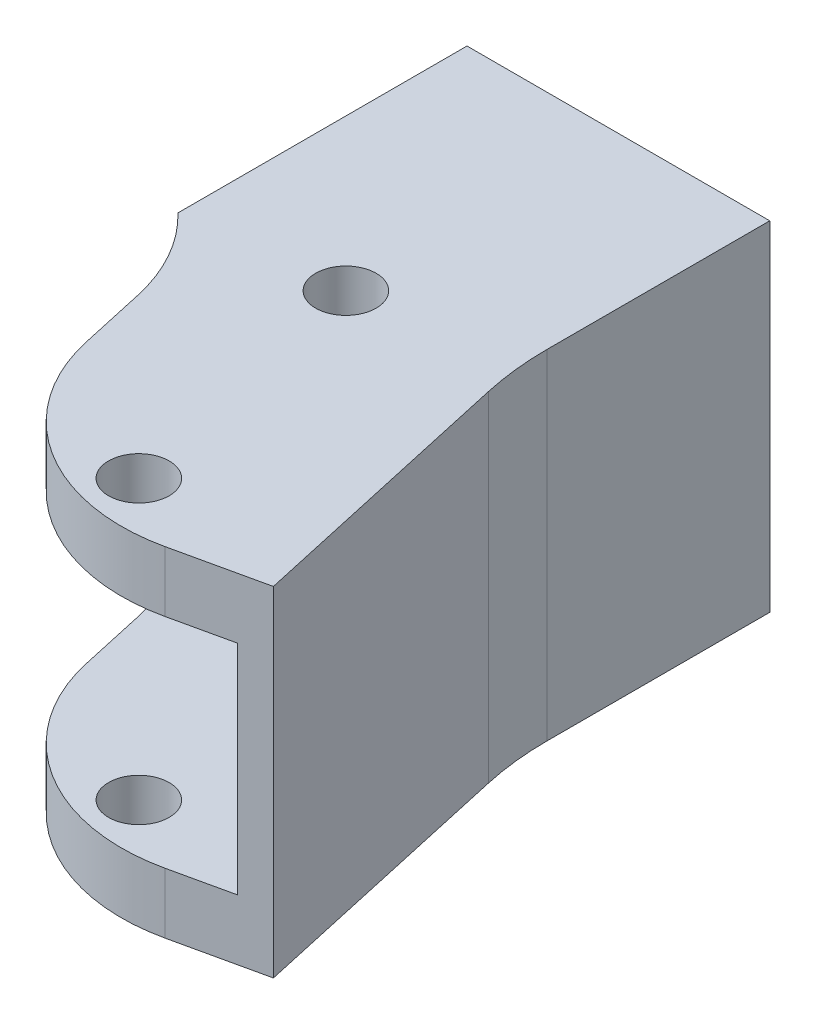
SolidWorks part; units mm, degrees
material "ABS"
ref_plane "正面" through (0, 0, 0) normal (0, 0, 1) x (1, 0, 0)
ref_plane "平面" through (0, 0, 0) normal (0, 1, 0) x (1, 0, 0)
ref_plane "右側面" through (0, 0, 0) normal (1, 0, 0) x (0, 0, -1)
sketch "ｽｹｯﾁ1" plane through (0, 0, 0) normal (0, 0, 1) x (1, 0, 0)
  line L1 (-20, 18) -> (20, 18)
  line L2 (-20, 18) -> (-20, -18)
  line L3 (-20, -18) -> (20, -18)
  line L4 (20, 18) -> (20, -18)
  line L5 (-20, 18) -> (20, -18) construction
  line L6 (-20, -18) -> (20, 18) construction
  circle A0 centre (0, 0) radius 8.5 construction
  circle A1 centre (0, 8.5) radius 1.6
  circle A2 centre (8.5, 0) radius 1.6
  circle A3 centre (0, -8.5) radius 1.6
  circle A4 centre (-8.5, 0) radius 1.6
  circle A5 centre (0, 0) radius 3.25
  point P0 (0, 0)
  point P19 (0, 0)
  dimension "D2" = 17
  dimension "D3" = 3.2
  dimension "D6" = 6.5
  dimension "D1" = 36
  dimension "D5" = 40
  dimension "D4" = 4
extrude "ﾎﾞｽ - 押し出し1" add sketch "ｽｹｯﾁ1" along normal blind 5
sketch "ｽｹｯﾁ2" plane through (0, 0, 5) normal (0, 0, 1) x (1, 0, 0)
  circle A0 centre (0, 0) radius 13
  dimension "D1" = 26
extrude "ｶｯﾄ - 押し出し1" cut sketch "ｽｹｯﾁ2" against normal blind 2.5
sketch "ｽｹｯﾁ7" plane through (0, -18, 0) normal (0, -1, 0) x (1, 0, 0)
  line L0 (-20, 0) -> (-20, 47.1904)
  line L1 (-20, 5) -> (-20, 0) construction
  line L2 (-20, 47.1904) -> (-7.6217, 103.0251)
  line L3 (-7.6217, 103.0251) -> (31.4301, 94.3675)
  line L4 (31.4301, 94.3675) -> (20, 42.8096)
  line L5 (20, 42.8096) -> (20, 0)
  line L6 (-20, 0) -> (20, 0) construction
  line L7 (20, 0) -> (-20, 0)
  line L8 (0, 0) -> (0, 42.348) construction
  line L9 (11.9042, 98.6963) -> (-8.4859, 6.7224) construction
  line L10 (20, 5) -> (20, 0) construction
  circle A0 centre (0, 45) radius 5
  circle A1 centre (9.7398, 88.9333) radius 5
  point P16 (-34.8258, 3.4356)
  point P19 (0, 0)
  point P20 (-30.3927, 17.0331)
  point P23 (0, 0)
  dimension "D1" = 10
  dimension "D4" = 10
  dimension "D2" = 40
  dimension "D3" = 45
  dimension "D5" = 12.5
  dimension "D6" = 45
extrude "ﾎﾞｽ - 押し出し2" add sketch "ｽｹｯﾁ7" along normal blind 10
sketch "ｽｹｯﾁ10" plane through (0, -18, 0) normal (0, 1, 0) x (1, 0, 0)
  circle A0 centre (0, -45) radius 5
  circle A1 centre (0, -45) radius 5 construction
extrude "ﾎﾞｽ - 押し出し4" add sketch "ｽｹｯﾁ10" against normal blind 2
mirror "ﾐﾗｰ3" about plane through (0, 0, 0) normal (0, 1, 0) of "ﾎﾞｽ - 押し出し4", "ﾎﾞｽ - 押し出し2"
sketch "ｽｹｯﾁ8" plane through (0, -28, 0) normal (0, -1, 0) x (1, 0, 0)
  line L0 (-7.6217, 103.0251) -> (-20, 47.1904) construction
  line L1 (-20, 47.1904) -> (-20, 0) construction
  line L2 (20, 42.8096) -> (31.4301, 94.3675) construction
  line L3 (20, 0) -> (20, 42.8096) construction
  line L4 (-7.6217, 103.0251) -> (-20, 47.1904) construction
  line L5 (-20, 47.1904) -> (-20, 0)
  line L6 (20, 42.8096) -> (31.4301, 94.3675)
  line L7 (20, 0) -> (20, 42.8096)
  line L8 (25, 0) -> (25, 42.2621)
  line L9 (25, 42.2621) -> (36.3116, 93.2853)
  line L10 (-12.5032, 104.1073) -> (-25, 47.7379) construction
  line L11 (-25, 47.7379) -> (-25, 0)
  line L12 (-25, 0) -> (-20, 0)
  line L13 (20, 0) -> (25, 0)
  line L14 (-12.5032, 104.1073) -> (-7.6217, 103.0251) construction
  line L15 (31.4301, 94.3675) -> (36.3116, 93.2853)
  line L16 (25, 42.2621) -> (20, 42.8096) construction
  line L17 (-20, 47.1904) -> (-25, 47.7379)
  dimension "D1" = 5
  dimension "D2" = 5
extrude "ﾎﾞｽ - 押し出し3" add sketch "ｽｹｯﾁ8" against normal up to surface (56 mm away) up to face at (14.7398, 28, 88.9333)
sketch "ｽｹｯﾁ9" plane through (0, 0, 5) normal (0, 0, 1) x (1, 0, 0)
  line L4 (20, -18) -> (20, 18)
  line L5 (20, 18) -> (-20, 18)
  line L6 (-20, 18) -> (-20, -18)
  line L7 (-20, -18) -> (20, -18)
  line L8 (20, -18) -> (20, 18)
  line L9 (20, 18) -> (-20, 18)
  line L10 (-20, 18) -> (-20, -18)
  line L11 (-20, -18) -> (20, -18)
  dimension "D1" = 0
fillet "ﾌｨﾚｯﾄ1" radius 30 6 edges at (-22.5, -28, 47.4642) (-22.5, 28, 47.4642) (-7.6217, -23, 103.0251) (-20, -23, 47.1904) (-20, 23, 47.1904) (-7.6217, 23, 103.0251)
fillet "ﾌｨﾚｯﾄ2" radius 50 1 edges at (25, 0, 42.2621)
fillet "ﾌｨﾚｯﾄ6" radius 5 2 edges at (-22.5, 18, 47.4642) (-22.5, -18, 47.4642)
